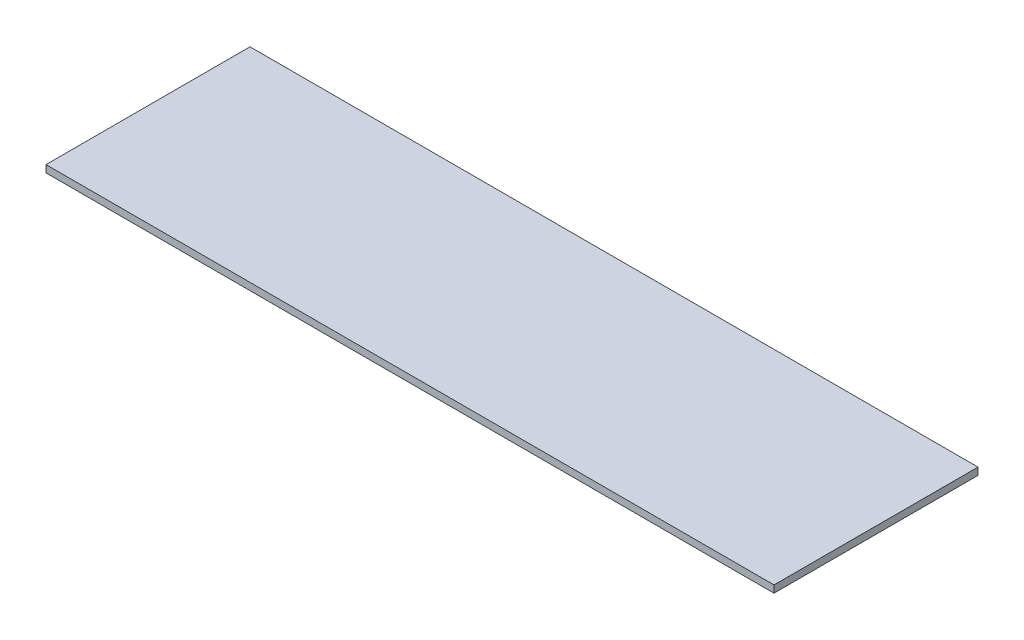
SolidWorks part; units mm, degrees
material "ABS"
ref_plane "Front Plane" through (0, 0, 0) normal (0, 0, 1) x (1, 0, 0)
ref_plane "Top Plane" through (0, 0, 0) normal (0, 1, 0) x (1, 0, 0)
ref_plane "Right Plane" through (0, 0, 0) normal (1, 0, 0) x (0, 0, -1)
sketch "Sketch1" plane through (0, 0, 0) normal (0, 1, 0) x (1, 0, 0)
  line L1 (0, 0) -> (1820, 0)
  line L2 (0, 0) -> (0, 510)
  line L3 (0, 510) -> (1820, 510)
  line L4 (1820, 0) -> (1820, 510)
  dimension "D1" = 510
  dimension "D2" = 1820
extrude "Boss-Extrude1" add sketch "Sketch1" along normal blind 18
